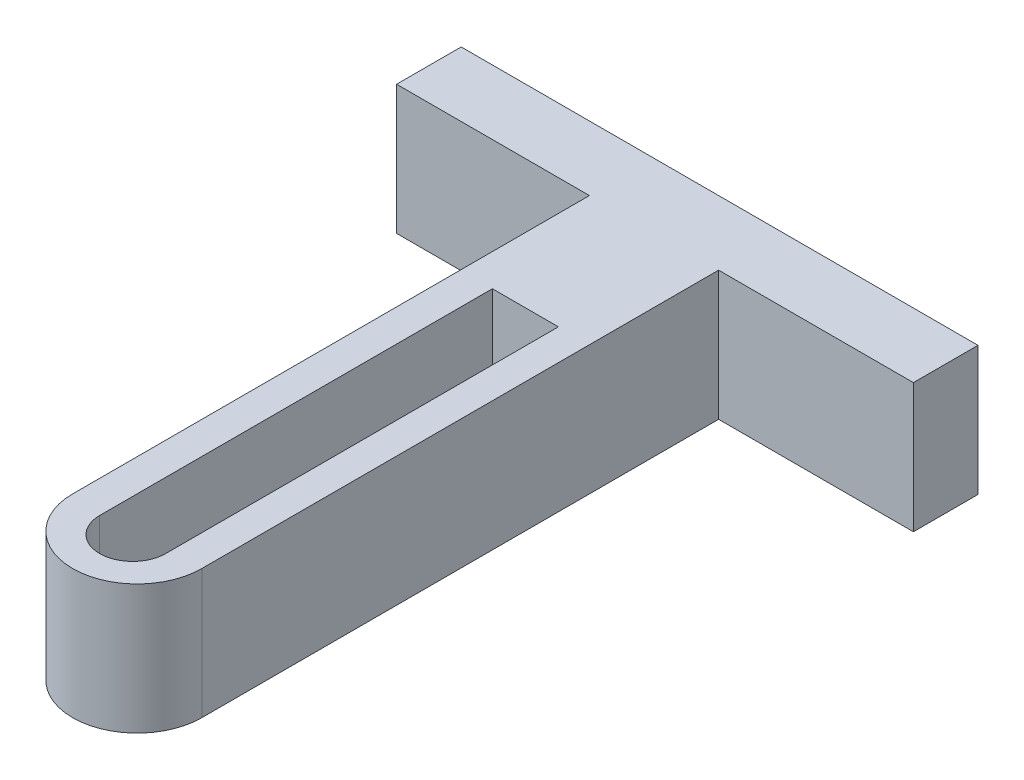
SolidWorks part; units mm, degrees
ref_plane "Front Plane" through (0, 0, 0) normal (0, 0, 1) x (1, 0, 0)
ref_plane "Top Plane" through (0, 0, 0) normal (0, 1, 0) x (1, 0, 0)
ref_plane "Right Plane" through (0, 0, 0) normal (1, 0, 0) x (0, 0, -1)
sketch "Sketch1" plane through (0, 0, 0) normal (0, 0, 1) x (1, 0, 0)
  line L1 (0, 0) -> (50.8, 0)
  line L2 (0, 0) -> (0, 12.7)
  line L3 (0, 12.7) -> (50.8, 12.7)
  line L4 (50.8, 0) -> (50.8, 12.7)
  dimension "D1" = 12.7
  dimension "D2" = 50.8
extrude "Boss-Extrude1" add sketch "Sketch1" along normal blind 6.35
ref_axis "Axis5" through (0, 6.35, 6.35) along (1, 0, 0)
ref_plane "Plane4" through (0, 6.35, 0) normal (0, -1, 0) x (1, 0, 0)
sketch "Sketch4" plane through (0, 0, 0) normal (0, -1, 0) x (1, 0, 0)
  line L0 (0, 6.35) -> (50.8, 6.35) construction
  line L2 (18.9535, 6.35) -> (31.6535, 6.35)
  line L3 (18.9535, 6.35) -> (18.9535, 57.15)
  line L5 (31.6535, 6.35) -> (31.6535, 57.15)
  line L7 (22.1173, 57.6533) -> (22.1173, 19.05)
  line L8 (22.1173, 19.05) -> (28.6055, 19.05)
  line L9 (28.6055, 57.6533) -> (28.6055, 19.05)
  arc A0 (18.9535, 57.15) -> (31.6535, 57.15) centre (25.3035, 57.15) cw
  arc A1 (22.1173, 57.6533) -> (28.6055, 57.6533) centre (25.3614, 57.6533) cw
  point P0 (25.4, 6.35)
  dimension "D1" = 50.8
  dimension "D2" = 12.7
  dimension "D3" = 3.1638
  dimension "D4" = 12.7
extrude "Boss-Extrude2" add sketch "Sketch4" against normal blind 12.7
